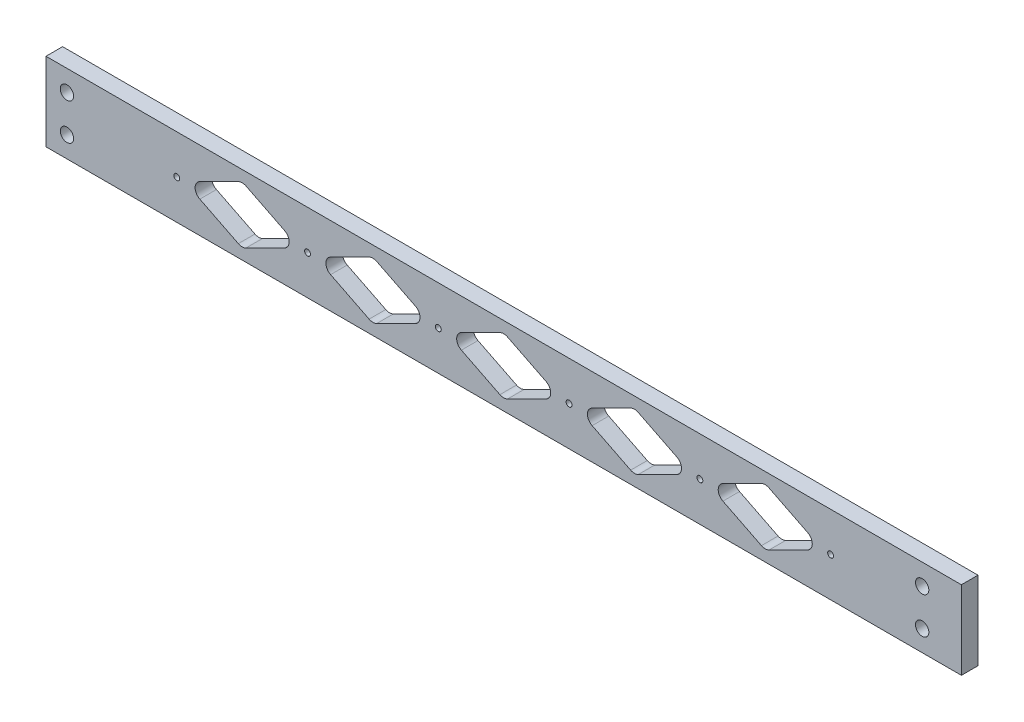
SolidWorks part; units mm, degrees
ref_plane "Front Plane" through (0, 0, 0) normal (0, 0, 1) x (1, 0, 0)
ref_plane "Top Plane" through (0, 0, 0) normal (0, 1, 0) x (1, 0, 0)
ref_plane "Right Plane" through (0, 0, 0) normal (1, 0, 0) x (0, 0, -1)
sketch "Sketch2" plane through (0, 0, 0) normal (0, 0, 1) x (1, 0, 0)
  line L1 (0, 0) -> (350, 0)
  line L2 (0, 0) -> (0, 30)
  line L3 (0, 30) -> (350, 30)
  line L4 (350, 0) -> (350, 30)
  dimension "D1" = 30
  dimension "D2" = 350
extrude "Boss-Extrude1" add sketch "Sketch2" along normal blind 6.35
sketch "Sketch3" plane through (0, 0, 6.35) normal (0, 0, 1) x (1, 0, 0)
  line L0 (8, 30) -> (8, 0) construction
  line L1 (350, 30) -> (0, 30) construction
  line L2 (0, 30) -> (0, 0) construction
  line L3 (0, 0) -> (350, 0) construction
  point P4 (8, 22)
  point P5 (8, 8)
  dimension "D1" = 8
  dimension "D2" = 8
  dimension "D3" = 8
hole_wizard "Tap Drill for 1/4-20 Tap2" positions "Sketch4" profile "Sketch5" hole size "1/4-20" standard "ANSI Inch" end condition through all
sketch "Sketch4" plane through (0, 0, 6.35) normal (0, 0, 1) x (1, 0, 0)
  point P0 (8, 22)
  point P3 (8, 8)
sketch "Sketch5" plane through (8, 22, 6.35) normal (1, 0, 0) x (0, -1, 0)
  line L0 (0, 0) -> (0, 6.35)
  line L1 (0, 6.35) -> (2.5527, 6.35)
  line L2 (2.5527, 6.35) -> (2.5527, 0)
  line L5 (2.5527, 0) -> (0, 0)
  line L11 (0, -6.35) -> (0, 107.95) construction
  dimension "Thru Hole Dia." = 5.1054
  dimension "Thru Hole Depth" = 6.35
sketch "Sketch6" plane through (0, 0, 6.35) normal (0, 0, 1) x (1, 0, 0)
  line L0 (0, 15) -> (350, 15) construction
  line L1 (0, 30) -> (0, 0) construction
  line L2 (350, 0) -> (350, 30) construction
  point P6 (50, 15)
  dimension "D1" = 50
hole_wizard "Tap Drill for #4-40 Tap1" positions "Sketch6" profile "Sketch7" hole size "#4-40" standard "ANSI Inch" end condition through all
sketch "Sketch7" plane through (50, 15, 6.35) normal (1, 0, 0) x (0, -1, 0)
  line L0 (0, 0) -> (0, 6.35)
  line L1 (0, 6.35) -> (1.1303, 6.35)
  line L2 (1.1303, 6.35) -> (1.1303, 0)
  line L5 (1.1303, 0) -> (0, 0)
  line L11 (0, -6.35) -> (0, 107.95) construction
  dimension "Thru Hole Dia." = 2.2606
  dimension "Thru Hole Depth" = 6.35
pattern_linear "LPattern1" count 6 spacing 50 along (1, 0, 0) of "Tap Drill for #4-40 Tap1"
sketch "Sketch8" plane through (0, 0, 0) normal (0, 0, -1) x (-1, 0, 0)
  line L0 (-335, 30) -> (-335, 0) construction
  line L1 (-350, 30) -> (0, 30) construction
  line L2 (0, 0) -> (-350, 0) construction
  line L3 (-350, 0) -> (-350, 30) construction
  point P6 (-335, 15)
  point P7 (-335, 22)
  point P8 (-335, 8)
  dimension "D1" = 15
  dimension "D2" = 7
  dimension "D3" = 7
hole_wizard "Tap Drill for 1/4-20 Tap1" positions "Sketch11" profile "Sketch12" hole size "1/4-20" standard "ANSI Inch" end condition through all
sketch "Sketch11" plane through (0, 0, 0) normal (0, 0, -1) x (-1, 0, 0)
  point P0 (-335, 22)
  point P3 (-335, 8)
sketch "Sketch12" plane through (335, 22, 0) normal (1, 0, 0) x (0, 1, 0)
  line L0 (0, 0) -> (0, 6.35)
  line L1 (0, 6.35) -> (2.5527, 6.35)
  line L2 (2.5527, 6.35) -> (2.5527, 0)
  line L5 (2.5527, 0) -> (0, 0)
  line L11 (0, -6.35) -> (0, 107.95) construction
  dimension "Thru Hole Dia." = 5.1054
  dimension "Thru Hole Depth" = 6.35
sketch "Sketch13" plane through (0, 0, 0) normal (0, 0, -1) x (-1, 0, 0)
  line L0 (-100, 15) -> (-50, 15) construction
  line L1 (-75, 4) -> (-75, 26)
  line L2 (-75, 26) -> (-97, 15)
  line L3 (-97, 15) -> (-75, 4)
  line L4 (-75, 26) -> (-53, 15)
  line L5 (-53, 15) -> (-75, 4)
  point P7 (-75, 15)
  dimension "D1" = 22
  dimension "D2" = 22
extrude "Cut-Extrude1" cut sketch "Sketch13" against normal through all contours L0 L3 L1 | L2 L0 L1 | L1 L0 L4 | L0 L1 L5 region at (82.3333, 18.6667, 0) region at (82.3333, 11.3333, 0) region at (67.6667, 18.6667, 0) region at (67.6667, 11.3333, 0)
fillet "Fillet1" radius 3.25 4 edges at (53, 15, 3.175) (75, 4, 3.175) (97, 15, 3.175) (75, 26, 3.175)
pattern_linear "LPattern2" count 5 spacing 50 along (1, 0, 0) of "Cut-Extrude1", "Fillet1"
